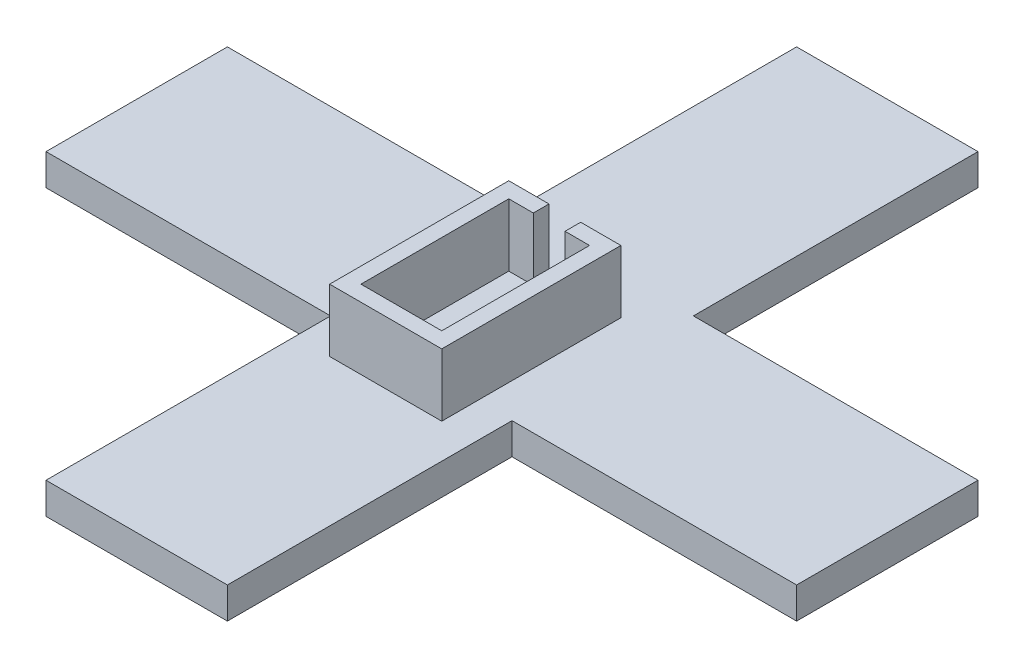
SolidWorks part; units mm, degrees
ref_plane "Front Plane" through (0, 0, 0) normal (0, 0, 1) x (1, 0, 0)
ref_plane "Top Plane" through (0, 0, 0) normal (0, 1, 0) x (1, 0, 0)
ref_plane "Right Plane" through (0, 0, 0) normal (1, 0, 0) x (0, 0, -1)
sketch "Sketch21" plane through (0, 0, 0) normal (0, 1, 0) x (1, 0, 0)
  line L22 (0, 59.92) -> (-14.48, 59.92)
  line L23 (-14.48, 59.92) -> (-14.48, 14.48)
  line L24 (-14.48, 14.48) -> (-59.92, 14.48)
  line L25 (-59.92, -14.48) -> (-14.48, -14.48)
  line L26 (-14.48, -14.48) -> (-14.48, -59.92)
  line L27 (-14.48, -59.92) -> (0, -59.92)
  line L28 (0, -59.92) -> (14.48, -59.92)
  line L29 (14.48, -59.92) -> (14.48, -14.48)
  line L30 (14.48, -14.48) -> (59.92, -14.48)
  line L31 (59.92, 14.48) -> (14.48, 14.48)
  line L32 (14.48, 14.48) -> (14.48, 59.92)
  line L33 (14.48, 59.92) -> (0, 59.92)
  line L34 (-59.92, 0) -> (-59.92, 14.48)
  line L35 (-59.92, -14.48) -> (-59.92, 0)
  line L36 (59.92, 0) -> (59.92, 14.48)
  line L37 (59.92, 0) -> (59.92, -14.48)
  dimension "D1" = 45.44
  dimension "D2" = 14.48
  dimension "D3" = 14.48
  dimension "D4" = 119.84
  dimension "D5" = 119.84
  dimension "D13" = 14.48
extrude "Boss-Extrude18" add sketch "Sketch21" along normal blind 5
sketch "Sketch23" plane through (0, 5, 0) normal (0, 1, 0) x (1, 0, 0)
  line L0 (-8.95, 8.435) -> (-2.53, 8.435)
  line L2 (-8.95, 8.435) -> (-8.95, -20.165)
  line L3 (-8.95, -20.165) -> (8.95, -20.165)
  line L4 (8.95, 8.435) -> (8.95, -20.165)
  line L5 (-2.53, 8.435) -> (-2.53, 5.935)
  line L6 (-2.53, 5.935) -> (-6.45, 5.935)
  line L7 (-6.45, 5.935) -> (-6.45, -17.665)
  line L8 (-6.45, -17.665) -> (6.45, -17.665)
  line L9 (6.45, -17.665) -> (6.45, 5.935)
  line L10 (6.45, 5.935) -> (2.53, 5.935)
  line L11 (2.53, 5.935) -> (2.53, 8.435)
  line L12 (2.53, 8.435) -> (8.95, 8.435)
  line L16 (14.48, 59.92) -> (-14.48, 59.92) construction
  point P0 (0, 0)
  dimension "D1" = 6.45
  dimension "D2" = 12.9
  dimension "D3" = 51.485
  dimension "D4" = 23.6
  dimension "D5" = 2.5
  dimension "D6" = 2.5
  dimension "D7" = 2.5
  dimension "D8" = 2.5
  dimension "D9" = 3.92
  dimension "D10" = 3.92
extrude "Boss-Extrude19" add sketch "Sketch23" along normal blind 10
